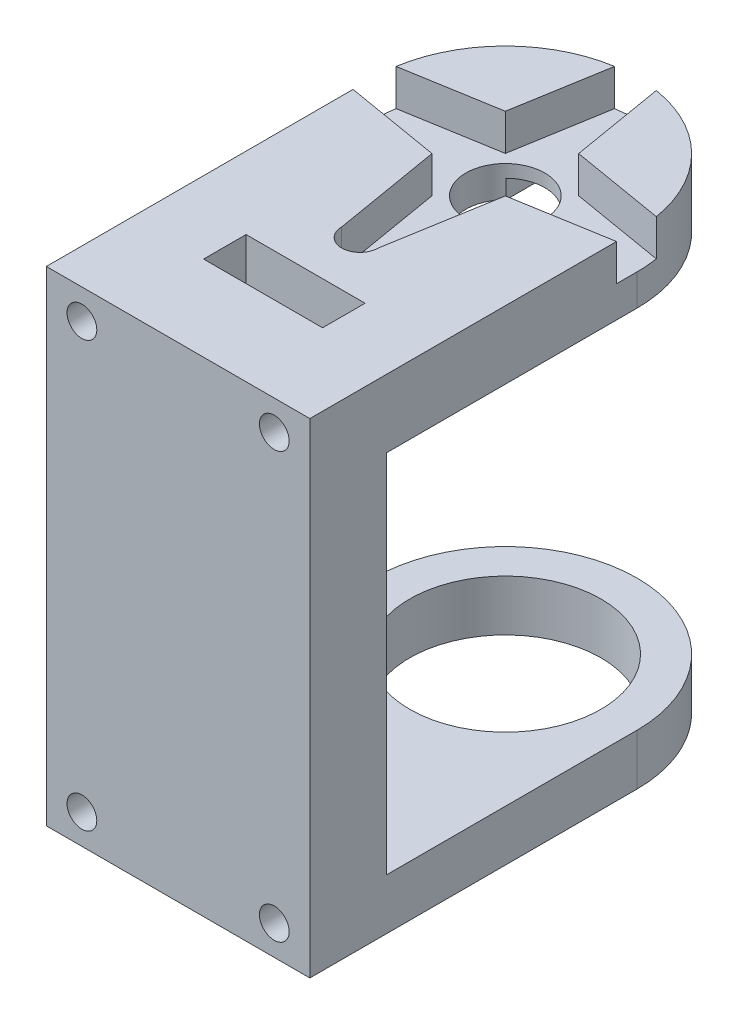
SolidWorks part; units mm, degrees
note: The reader was unsure of these and kept them because the rebuilt part matched: shared geometry of "Sketch6<3>", "Sketch9<3>".
ref_plane "Front Plane" through (0, 0, 0) normal (0, 0, 1) x (1, 0, 0)
ref_plane "Top Plane" through (0, 0, 0) normal (0, 1, 0) x (1, 0, 0)
ref_plane "Right Plane" through (0, 0, 0) normal (1, 0, 0) x (0, 0, -1)
sketch "Sketch1" plane through (0, 0, 0) normal (0, 0, 1) x (1, 0, 0)
  line L0 (-15.5, -28.5) -> (-8.5, -28.5) construction
  line L1 (15.5, -28.5) -> (-15.5, -28.5)
  line L2 (15.5, -28.5) -> (15.5, 28.5)
  line L3 (15.5, 28.5) -> (-15.5, 28.5)
  line L4 (-15.5, -28.5) -> (-15.5, -10.3)
  line L5 (15.5, -28.5) -> (-15.5, 28.5) construction
  line L6 (-15.5, 10.3) -> (-15.5, -10.3)
  line L8 (-15.5, -28.5) -> (-15.5, -10.3) construction
  line L13 (-15.5, 10.3) -> (-15.5, 28.5)
  point P0 (0, 0)
  dimension "D1" = 31
  dimension "D2" = 57
  dimension "D3" = 7
  dimension "D4" = 15.5
  dimension "D7" = 18.2
extrude "Boss-Extrude1" add sketch "Sketch1" along normal blind 9
sketch "Sketch4" plane through (0, 0, 0) normal (0, 0, -1) x (-1, 0, 0)
  line L0 (15.5, 28.5) -> (15.5, -28.5) construction
  line L1 (-15.5, 28.5) -> (15.5, 28.5)
  line L2 (-15.5, 28.5) -> (-15.5, 20.5)
  line L3 (-15.5, 20.5) -> (15.5, 20.5)
  line L4 (15.5, 28.5) -> (15.5, 20.5)
  line L5 (15.5, 28.5) -> (15.5, -28.5) construction
  line L6 (-15.5, -28.5) -> (15.5, -28.5)
  line L7 (-15.5, -28.5) -> (-15.5, -22.5)
  line L8 (-15.5, -22.5) -> (15.5, -22.5)
  line L9 (15.5, -28.5) -> (15.5, -22.5)
  dimension "D1" = 8
  dimension "D2" = 6
extrude "Boss-Extrude4" add sketch "Sketch4" along normal blind 45
sketch "Sketch6" plane through (0, -28.5, 0) normal (0, -1, 0) x (1, 0, 0)
  line L0 (0, 0) -> (0, -29.5) construction
  line L1 (15.5, 9) -> (15.5, -45) construction
  line L2 (-15.5, -29.5) -> (-15.5, -45)
  line L3 (-15.5, -45) -> (15.5, -45)
  line L4 (15.5, -45) -> (-15.5, -45) construction
  line L5 (15.5, -45) -> (15.5, -29.5)
  arc A0 (15.5, -29.5) -> (-15.5, -29.5) centre (0, -29.5) cw
  circle A1 centre (0, -29.5) radius 11.25
  line M2 (-15.5, 9) -> (-15.5, -45)
  line M3 (-15.5, -45) -> (15.5, -45)
  line M4 (15.5, -45) -> (15.5, 9)
  dimension "D2" = 15.5
  dimension "D3" = 22.5
  dimension "D1" = 29.5
extrude "Cut-Extrude1" cut sketch "Sketch6" against normal through all contours A0 L3 M4 | A0 M3 M2
extrude "Cut-Extrude2" cut sketch "Sketch6<3>" against normal blind 6
sketch "Sketch6<3>" plane through (0, -28.5, 0) normal (0, -1, 0) x (1, 0, 0) same geometry as "Sketch6"
sketch "Sketch7" plane through (0, 28.5, 0) normal (0, 1, 0) x (1, 0, 0)
  line L0 (0, 0) -> (0, 29.5) construction
  line L1 (0, 29.5) -> (0, 12.4) construction
  line L2 (0, 29.5) -> (17.1, 29.5) construction
  line L3 (0, 29.5) -> (0, 46.6) construction
  line L4 (0, 29.5) -> (-17.1, 29.5) construction
  line L5 (-17.1, 31.65) -> (-4.3134, 33.8134)
  line L6 (-4.3134, 33.8134) -> (-2.15, 46.6)
  line L7 (-4.3134, 25.1866) -> (-2.15, 12.4)
  line L8 (-17.1, 27.35) -> (-4.3134, 25.1866)
  line L9 (4.3134, 25.1866) -> (2.15, 12.4)
  line L10 (17.1, 27.35) -> (4.3134, 25.1866)
  line L11 (17.1, 31.65) -> (4.3134, 33.8134)
  line L12 (4.3134, 33.8134) -> (2.15, 46.6)
  arc A1 (-2.15, 12.4) -> (2.15, 12.4) centre (0, 12.4) ccw
  arc A2 (2.15, 46.6) -> (-2.15, 46.6) centre (0, 46.6) ccw
  arc A3 (17.1, 27.35) -> (17.1, 31.65) centre (17.1, 29.5) ccw
  arc A4 (-17.1, 31.65) -> (-17.1, 27.35) centre (-17.1, 29.5) ccw
  arc A5 (4.3134, 25.1866) -> (6.1, 29.5) centre (0, 29.5) ccw construction
  dimension "D4" = 4.3
  dimension "D8" = 4.3
  dimension "D9" = 4.3
  dimension "D10" = 4.3
  dimension "D11" = 12.2
  dimension "D1" = 29.5
  dimension "D3" = 17.1
  dimension "D5" = 17.1
  dimension "D6" = 17.1
  dimension "D7" = 17.1
  dimension "D12" = 24.1142
extrude "Cut-Extrude3" cut sketch "Sketch7" against normal blind 4.3
sketch "Sketch9" plane through (0, 20.5, 0) normal (0, -1, 0) x (1, 0, 0)
  line L0 (0, 0) -> (0, -29.5) construction
  line L1 (15.5, 0) -> (-15.5, 0) construction
  line L2 (3.25, -29.5) -> (-3.25, -29.5) construction
  line L3 (-3.25, -29.5) -> (-3.25, -32.8257) construction
  line L4 (3.25, -29.5) -> (3.25, -32.8257) construction
  line L5 (-3.25, -32.8257) -> (-3.25, -44.6554)
  line L6 (3.25, -32.8257) -> (3.25, -44.6554)
  circle A0 centre (0, -29.5) radius 4.65
  arc A1 (-15.5, -29.5) -> (15.5, -29.5) centre (0, -29.5) ccw construction
  dimension "D2" = 9.3
  dimension "D1" = 29.5
  dimension "D3" = 3.25
extrude "Cut-Extrude4" cut sketch "Sketch9" against normal blind 2.2 contours A0 L5 L4 L6
extrude "Cut-Extrude5" cut sketch "Sketch9<3>" against normal blind 8 contours A0
sketch "Sketch9<3>" plane through (0, 20.5, 0) normal (0, -1, 0) x (1, 0, 0) same geometry as "Sketch9"
sketch "Sketch13" plane through (0, 28.5, 0) normal (0, 1, 0) x (1, 0, 0)
  line L0 (0, 0) -> (0, 3.5) construction
  line L2 (7, 1) -> (-7, 1)
  line L3 (7, 1) -> (7, 6)
  line L4 (7, 6) -> (-7, 6)
  line L5 (-7, 1) -> (-7, 6)
  line L6 (7, 1) -> (-7, 6) construction
  line L7 (7, 6) -> (-7, 1) construction
  dimension "D1" = 3.5
  dimension "D2" = 5
  dimension "D3" = 14
extrude "Cut-Extrude8" cut sketch "Sketch13" against normal blind 9
sketch "Sketch14" plane through (0, 0, 9) normal (0, 0, 1) x (1, 0, 0)
  line L0 (0, 0) -> (15.5, 0) construction
  line L1 (15.5, -28.5) -> (15.5, 28.5) construction
  line L2 (0, 0) -> (0, 28.5) construction
  line L3 (15.5, 28.5) -> (-15.5, 28.5) construction
  line L4 (15.5, 0) -> (11.3164, 0) construction
  line L5 (11.3164, 0) -> (11.3164, 25) construction
  circle A0 centre (11.3164, 25) radius 1.75
  circle A1 centre (-11.3164, 25) radius 1.75
  circle A2 centre (11.3164, -25) radius 1.75
  circle A3 centre (-11.3164, -25) radius 1.75
  dimension "D2" = 3.5
  dimension "D1" = 25
  dimension "D3" = 11.3164
extrude "Cut-Extrude9" cut sketch "Sketch14" against normal blind 3
